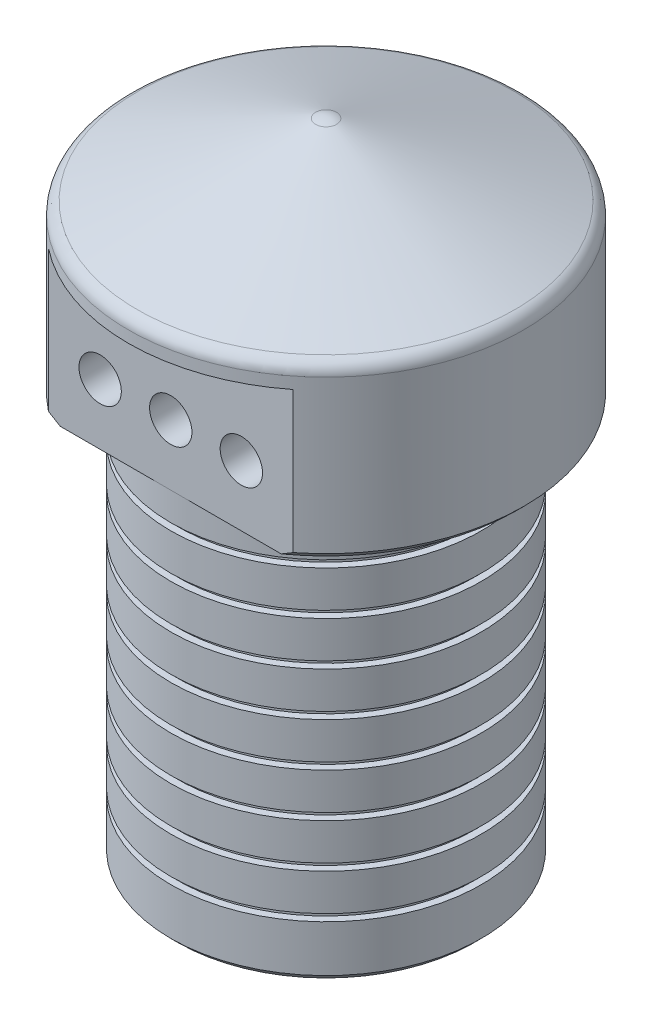
SolidWorks part; units mm, degrees
material "6061-T4 (SS)"
ref_plane "前视基准面" through (0, 0, 0) normal (0, 0, 1) x (1, 0, 0)
ref_plane "上视基准面" through (0, 0, 0) normal (0, 1, 0) x (1, 0, 0)
ref_plane "右视基准面" through (0, 0, 0) normal (1, 0, 0) x (0, 0, -1)
sketch "草图1" plane through (0, 0, 0) normal (0, 1, 0) x (1, 0, 0)
  circle A0 centre (0, 0) radius 11
  dimension "D1" = 22
extrude "凸台-拉伸1" add sketch "草图1" along normal blind 28
sketch "草图2" plane through (0, 28, 0) normal (0, 1, 0) x (1, 0, 0)
  circle A0 centre (0, 0) radius 14
  dimension "D1" = 28
extrude "凸台-拉伸2" add sketch "草图2" along normal blind 12
sketch "草图3" plane through (0, 0, 0) normal (0, 0, 1) x (1, 0, 0)
  line L0 (0, 0) -> (0, 45.4459) construction
  line L1 (-14, 40) -> (0, 40)
  line L2 (14, 40) -> (-14, 40) construction
  line L3 (0, 40) -> (0, 45.4459)
  line L4 (-0.7428, 45.3029) -> (-14, 40)
  line L5 (0, 45.4459) -> (2.4384, 45.4459) construction
  arc A0 (-0.7428, 45.3029) -> (0, 45.4459) centre (0, 43.4459) cw
  dimension "D2" = 2
  dimension "D1" = 21.801
revolve "旋转1" add sketch "草图3" angle 360 about L0
fillet "圆角1" radius 1 1 edges at (0, 40, 14)
chamfer "倒角1" distance 0.5 angle 45 2 edges at (0, 28, 14) (0, 0, 11)
sketch "草图4" plane through (0, 0, 0) normal (1, 0, 0) x (0, 0, -1)
  line L0 (0, 0) -> (0, 45.4459) construction
  line L1 (-10.5, 0) -> (10.5, 0) construction
  line L2 (-11, 28) -> (-11, 0.5) construction
  line L3 (-11, 26) -> (-10.5, 26)
  line L4 (-11, 26) -> (-11, 25.5)
  line L5 (-11, 25.5) -> (-10.5, 25.5)
  line L6 (-10.5, 26) -> (-10.5, 25.5)
  line L7 (-11, 28) -> (11, 28) construction
  line L8 (-11, 22.9) -> (-11, 22.4)
  line L9 (-11, 22.9) -> (-10.5, 22.9)
  line L10 (-10.5, 22.9) -> (-10.5, 22.4)
  line L11 (-11, 22.4) -> (-10.5, 22.4)
  line L12 (-11, 19.8) -> (-11, 19.3)
  line L13 (-11, 19.8) -> (-10.5, 19.8)
  line L14 (-10.5, 19.8) -> (-10.5, 19.3)
  line L15 (-11, 19.3) -> (-10.5, 19.3)
  line L16 (-11, 16.7) -> (-11, 16.2)
  line L17 (-11, 16.7) -> (-10.5, 16.7)
  line L18 (-10.5, 16.7) -> (-10.5, 16.2)
  line L19 (-11, 16.2) -> (-10.5, 16.2)
  line L20 (-11, 13.6) -> (-11, 13.1)
  line L21 (-11, 13.6) -> (-10.5, 13.6)
  line L22 (-10.5, 13.6) -> (-10.5, 13.1)
  line L23 (-11, 13.1) -> (-10.5, 13.1)
  line L24 (-11, 10.5) -> (-11, 10)
  line L25 (-11, 10.5) -> (-10.5, 10.5)
  line L26 (-10.5, 10.5) -> (-10.5, 10)
  line L27 (-11, 10) -> (-10.5, 10)
  line L28 (-11, 7.4) -> (-11, 6.9)
  line L29 (-11, 7.4) -> (-10.5, 7.4)
  line L30 (-10.5, 7.4) -> (-10.5, 6.9)
  line L31 (-11, 6.9) -> (-10.5, 6.9)
  line L32 (-11, 4.3) -> (-11, 3.8)
  line L33 (-11, 4.3) -> (-10.5, 4.3)
  line L34 (-10.5, 4.3) -> (-10.5, 3.8)
  line L35 (-11, 3.8) -> (-10.5, 3.8)
  arc A0 (0.7428, 45.3029) -> (-0.7428, 45.3029) centre (0, 43.4459) ccw construction
  dimension "D1" = 0.5
  dimension "D2" = 0.5
  dimension "D3" = 2
  dimension "D5" = 2.6
  dimension "D4" = 8
revolve "切除-旋转1" cut sketch "草图4" angle 360 about L0
sketch "草图5" plane through (0, 0, 0) normal (0, -1, 0) x (1, 0, 0)
  circle A0 centre (0, 0) radius 9
  dimension "D1" = 18
extrude "切除-拉伸1" cut sketch "草图5" against normal blind 29
sketch "草图6" plane through (0, 29, 0) normal (0, -1, 0) x (1, 0, 0)
  circle A0 centre (0, 0) radius 3
  dimension "D1" = 6
extrude "切除-拉伸2" cut sketch "草图6" against normal blind 5
sketch "草图7" plane through (0, 0, 0) normal (0, 1, 0) x (1, 0, 0)
  line L1 (-22.2921, -23.6078) -> (19.9604, -23.6078)
  line L2 (-22.2921, -23.6078) -> (-22.2921, -11)
  line L3 (-22.2921, -11) -> (19.9604, -11)
  line L4 (19.9604, -23.6078) -> (19.9604, -11)
  circle A2 centre (0, 0) radius 14 construction
  dimension "D1" = 25
extrude "切除-拉伸3" cut sketch "草图7" along normal blind 10.5 and the other way blind 2.2 from surface starting at face at (0, 28, 13.5)
sketch "草图8" plane through (0, 0, 11) normal (0, 0, 1) x (1, 0, 0)
  line L0 (0, 0) -> (0, 41.0351) construction
  line L1 (-10.5, 0) -> (10.5, 0) construction
  line L2 (-7.2256, 32.3) -> (10.9717, 32.3) construction
  line L4 (-8.6603, 38.5) -> (8.6603, 38.5) construction
  circle A0 centre (0, 32.3) radius 1.5
  circle A1 centre (-5, 32.3) radius 1.5
  circle A2 centre (5, 32.3) radius 1.5
  dimension "D1" = 3
  dimension "D2" = 10
  dimension "D3" = 6.2
extrude "切除-拉伸4" cut sketch "草图8" against normal blind 10.5 contours A0 region at (0, 32.3, 11)
extrude "切除-拉伸5" cut sketch "草图8<3>" against normal through all contours A1 | A2 region at (-5, 32.3, 11) region at (5, 32.3, 11)
sketch "草图8<3>" plane through (0, 0, 11) normal (0, 0, 1) x (1, 0, 0) same geometry as "草图8"
sketch "草图9" plane through (0, 0, 0) normal (0, 0, 1) x (1, 0, 0)
  circle A0 centre (5, 32.3) radius 2.75
  circle A1 centre (-5, 32.3) radius 2.75
  dimension "D1" = 5.5
extrude "切除-拉伸6" cut sketch "草图9" against normal blind 10.5 from offset 7 offset against normal yes
